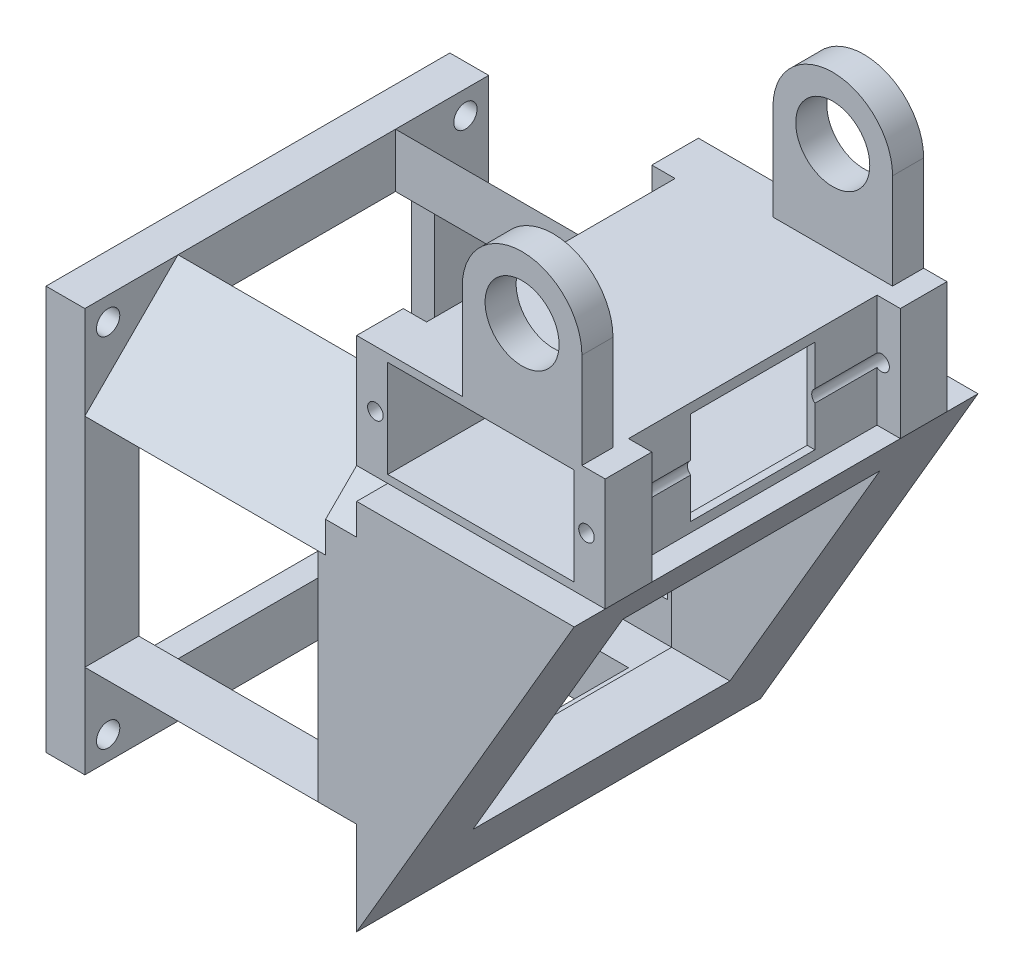
SolidWorks part; units mm, degrees
material "ABS"
ref_plane "Front Plane" through (0, 0, 0) normal (0, 0, 1) x (1, 0, 0)
ref_plane "Top Plane" through (0, 0, 0) normal (0, 1, 0) x (1, 0, 0)
ref_plane "Right Plane" through (0, 0, 0) normal (1, 0, 0) x (0, 0, -1)
sketch "Sketch1" plane through (0, 0, 0) normal (0, 0, 1) x (1, 0, 0)
  line L1 (0, 0) -> (24, 0)
  line L2 (0, 0) -> (0, 12.5)
  line L3 (0, 12.5) -> (24, 12.5)
  line L4 (24, 0) -> (24, 12.5)
  line L5 (-1, -1) -> (25, -1)
  line L6 (-1, -1) -> (-1, 13.5)
  line L7 (-1, 13.5) -> (25, 13.5)
  line L8 (25, -1) -> (25, 13.5)
  dimension "D1" = 24
  dimension "D2" = 12.5
  dimension "D3" = 1
  dimension "D4" = 1
  dimension "D5" = 1
  dimension "D6" = 1
extrude "Boss-Extrude1" add sketch "Sketch1" along normal blind 22
sketch "Sketch2" plane through (0, 0, 22) normal (0, 0, 1) x (1, 0, 0)
  line L0 (12, -1) -> (12, 13.5) construction
  line L1 (-1, 13.5) -> (-4, 13.5)
  line L2 (-1, 13.5) -> (-1, -1)
  line L3 (-1, -1) -> (-4, -1)
  line L4 (-4, 13.5) -> (-4, -1)
  line L5 (-1, -1) -> (25, -1) construction
  line L6 (25, 13.5) -> (-1, 13.5) construction
  line L7 (25, -1) -> (28, -1)
  line L8 (28, 13.5) -> (28, -1)
  line L9 (25, 13.5) -> (28, 13.5)
  line L10 (25, 13.5) -> (25, -1)
  dimension "D1" = 3
  dimension "D2" = 14.5
extrude "Boss-Extrude2" add sketch "Sketch2" against normal blind 6
mirror "Mirror2" about plane through (0, 0, 0) normal (0, 0, -1) of "Boss-Extrude2", "Boss-Extrude1"
sketch "Sketch3" plane through (-1, 0, 0) normal (-1, 0, 0) x (0, 0, 1)
  line L0 (0, -1) -> (0, 13.5) construction
  line L1 (16, -1) -> (-16, -1) construction
  line L2 (16, 13.5) -> (-16, 13.5) construction
  line L4 (-8, 0.25) -> (8, 0.25)
  line L5 (-8, 0.25) -> (-8, 12.25)
  line L6 (-8, 12.25) -> (8, 12.25)
  line L7 (8, 0.25) -> (8, 12.25)
  line L8 (-8, 0.25) -> (8, 12.25) construction
  line L9 (-8, 12.25) -> (8, 0.25) construction
  point P6 (0, 6.25)
  dimension "D1" = 16
  dimension "D2" = 12
extrude "Cut-Extrude1" cut sketch "Sketch3" against normal up to surface (26 mm away) up to face at (25, 6.25, 0)
sketch "Sketch4" plane through (0, 0, 22) normal (0, 0, 1) x (1, 0, 0)
  line L0 (12, 13.5) -> (12, -1) construction
  line L1 (28, 13.5) -> (-4, 13.5) construction
  line L2 (-4, -1) -> (28, -1) construction
  circle A0 centre (-1.59, 6.25) radius 1
  circle A1 centre (25.59, 6.25) radius 1
  dimension "D2" = 2
  dimension "D1" = 13.59
  dimension "D3" = 7.25
extrude "Cut-Extrude2" cut sketch "Sketch4" against normal up to surface (44 mm away)
sketch "Sketch5" plane through (0, 0, 0) normal (1, 0, 0) x (0, 0, -1)
  line L0 (0, 0) -> (0, -48.5226) construction
  line L5 (-16, -1) -> (16, -1) construction
  line L6 (-22, -45) -> (22, -45)
  line L7 (-22, -45) -> (-22, -1)
  line L8 (-22, -1) -> (22, -1)
  line L9 (22, -45) -> (22, -1)
  line L10 (-22, -45) -> (22, -1) construction
  line L11 (-22, -1) -> (22, -45) construction
  line L13 (-19.05, -3.95) -> (19.05, -3.95)
  line L14 (-19.05, -3.95) -> (-19.05, -42.05)
  line L15 (-19.05, -42.05) -> (19.05, -42.05)
  line L16 (19.05, -3.95) -> (19.05, -42.05)
  point P2 (0, -23)
  dimension "D1" = 44
  dimension "D2" = 44
  dimension "D3" = 38.1
  dimension "D4" = 38.1
  dimension "D5" = 2.95
  dimension "D6" = 2.95
extrude "Boss-Extrude3" add sketch "Sketch5" against normal blind 40
sketch "Sketch6" plane through (-40, 0, 0) normal (-1, 0, 0) x (0, 0, 1)
  line L0 (16, -1) -> (-16, -1) construction
  line L2 (22, -1) -> (22, -45) construction
  circle A0 centre (0, -23) radius 25
  dimension "D1" = 50
  dimension "D2" = 22
  dimension "D3" = 22
sketch "Sketch8" plane through (-40, 0, 0) normal (-1, 0, 0) x (0, 0, 1)
  line L0 (-22, -1) -> (22, -1) construction
  line L1 (-26, 3) -> (26, 3)
  line L2 (-26, 3) -> (-26, -49)
  line L3 (-26, -49) -> (26, -49)
  line L4 (26, 3) -> (26, -49)
  line L5 (22, -1) -> (22, -45) construction
  line L6 (0, -1) -> (0, -23)
  line L7 (-22, -1) -> (22, -1)
  line L8 (-22, -1) -> (-22, -45)
  line L9 (-22, -45) -> (22, -45)
  line L10 (22, -1) -> (22, -45)
  line M12 (22, -1) -> (-22, -1)
  line M13 (-22, -1) -> (-22, -45)
  line M22 (-22, -45) -> (22, -45)
  line M23 (22, -45) -> (22, -1)
  dimension "D1" = 52
  dimension "D2" = 52
  dimension "D3" = 4
  dimension "D4" = 4
  dimension "D8" = 22
extrude "Boss-Extrude5" add sketch "Sketch8" against normal up to surface (36 mm away) contours L4 L1 L2 L3 M13 M12 M23 M22 region at (-40, 2.2646, 0) up to face at (-4, 6.25, -19)
extrude "Cut-Extrude5" cut sketch "Sketch6" against normal blind 2
sketch "Sketch9" plane through (-4, 0, 0) normal (1, 0, 0) x (0, 0, -1)
  line L2 (-26, -49) -> (26, -49)
  line L6 (22, -45) -> (-22, -45)
  line L8 (-22, -1) -> (-26, -1)
  line L9 (-26, 3) -> (-26, -49) construction
  line L10 (-26, -1) -> (-26, -49)
  line L11 (22, -1) -> (26, -1)
  line L12 (26, 3) -> (26, -49) construction
  line L13 (26, -1) -> (26, -49)
  line L14 (22, -1) -> (22, -45)
  line L15 (-22, -1) -> (-22, -45)
extrude "Boss-Extrude6" add sketch "Sketch9" along normal up to surface (4 mm away) up to face at (0, -23, 0)
chamfer "Chamfer1" distance 12 angle 45 4 edges at (-22, 3, 26) (-22, 3, -26) (-20, -49, -26) (-20, -49, 26)
sketch "Sketch11" plane through (0, 0, 26) normal (0, 0, 1) x (1, 0, 0)
  line L8 (-40, -9) -> (-40, 3) construction
  line L9 (-35, -9) -> (-5, -9)
  line L10 (-35, -9) -> (-35, -37)
  line L11 (-35, -37) -> (-5, -37)
  line L12 (-5, -9) -> (-5, -37)
  line L14 (0, -37) -> (0, -1) construction
  line L16 (-4, -9) -> (-40, -9) construction
  line L17 (-40, -37) -> (0, -37) construction
  dimension "D2" = 5
  dimension "D3" = 5
extrude "Cut-Extrude7" cut sketch "Sketch11" against normal up to surface (52 mm away) contours L10 L11 L12 L9 up to face at (-14.6667, -15.6667, -26)
sketch "Sketch12" plane through (0, 3, 0) normal (0, 1, 0) x (1, 0, 0)
  line L0 (-4, 14) -> (-40, 14) construction
  line L1 (-35, 14) -> (-5, 14)
  line L2 (-35, 14) -> (-35, -14)
  line L3 (-35, -14) -> (-5, -14)
  line L4 (-5, 14) -> (-5, -14)
  line L5 (-40, -14) -> (-4, -14) construction
  line L6 (0, 22) -> (0, 26) construction
  line L7 (-40, 14) -> (-40, -14) construction
  dimension "D1" = 5
  dimension "D2" = 5
extrude "Cut-Extrude8" cut sketch "Sketch12" against normal up to surface (52 mm away) up to face at (-20, -49, 0)
chamfer "Chamfer3" distance 4 2 edges at (-2, -1, -26) (-2, -1, 26)
sketch "Sketch14" plane through (-40, 0, 0) normal (-1, 0, 0) x (0, 0, 1)
  line L0 (-26, -9) -> (-26, 3)
  line L1 (-26, 3) -> (-14, 3)
  line L2 (-14, 3) -> (-26, -9)
  line L3 (0, -3.95) -> (0, -22.95)
  line L4 (-16.1894, -3.95) -> (16.1894, -3.95) construction
  line L5 (26, -9) -> (14, 3)
  line L6 (14, 3) -> (26, 3)
  line L7 (26, 3) -> (26, -9)
  line L8 (14, -49) -> (26, -37)
  line L9 (26, -37) -> (26, -49)
  line L10 (26, -49) -> (14, -49)
  line L11 (-26, -37) -> (-14, -49)
  line L12 (-14, -49) -> (-26, -49)
  line L13 (-26, -49) -> (-26, -37)
  line L14 (-14, 3) -> (14, 3) construction
  line L15 (26, -9) -> (26, -37) construction
  circle A0 centre (-23, 0) radius 1.5
  circle A1 centre (23, 0) radius 1.5
  circle A2 centre (23, -46) radius 1.5
  circle A3 centre (-23, -46) radius 1.5
  point P30 (0, -23)
  line M19 (-14, 3) -> (-26, -9)
  line M21 (-26, -37) -> (-14, -49)
  line M23 (14, -49) -> (26, -37)
  line M25 (26, -9) -> (14, 3)
  dimension "D1" = 3
  dimension "D2" = 3
  dimension "D3" = 3
  dimension "D4" = 19
  dimension "D5" = 4
extrude "Boss-Extrude7" add sketch "Sketch14" against normal blind 5 contours L1 L0 A0 M19 | L7 L6 L5 A1 M25 | L10 L9 A2 M23 | L13 L12 A3 M21 region at (-40, -1.1089, -21.8911) region at (-40, -1.1089, 21.8911) region at (-40, -44.8911, 21.8911) region at (-40, -44.8911, -21.8911)
sketch "Sketch15" plane through (0, 0, 0) normal (1, 0, 0) x (0, 0, -1)
  line L1 (-19.05, -3.95) -> (19.05, -3.95)
  line L2 (-19.05, -3.95) -> (-19.05, -42.05)
  line L3 (-19.05, -42.05) -> (19.05, -42.05)
  line L4 (19.05, -3.95) -> (19.05, -42.05)
  line L5 (-16.55, -6.45) -> (16.55, -6.45)
  line L6 (-16.55, -6.45) -> (-16.55, -39.55)
  line L7 (-16.55, -39.55) -> (16.55, -39.55)
  line L8 (16.55, -6.45) -> (16.55, -39.55)
  dimension "D1" = 2.5
  dimension "D2" = 2.5
  dimension "D3" = 2.5
  dimension "D4" = 2.5
extrude "Boss-Extrude8" add sketch "Sketch15" against normal blind 2
sketch "Sketch16" plane through (0, 13.5, 0) normal (0, 1, 0) x (1, 0, 0)
  line L0 (0, 0) -> (25, 0) construction
  line L1 (25, -16) -> (25, 16) construction
  line L7 (25, -18) -> (9.6, -18)
  line L8 (28, 22) -> (-4, 22) construction
  line L18 (9.6, -22) -> (9.6, -18)
  line L19 (25, 22) -> (9.6, 22)
  line L20 (25, 22) -> (25, 18)
  line L21 (25, 18) -> (9.6, 18)
  line L22 (9.6, 22) -> (9.6, 18)
  line L23 (25, -22) -> (9.6, -22)
  line L24 (25, -22) -> (25, -18)
  dimension "D1" = 4
  dimension "D2" = 15.4
extrude "Boss-Extrude9" add sketch "Sketch16" along normal blind 20
sketch "Sketch18" plane through (0, 0, 22) normal (0, 0, 1) x (1, 0, 0)
  line L0 (25, 33.5) -> (25, 13.5) construction
  line L2 (9.6, 13.5) -> (-4, 13.5) construction
  circle A0 centre (17.3, 25.5) radius 4.765
  dimension "D1" = 9.53
  dimension "D2" = 7.7
  dimension "D3" = 12
extrude "Cut-Extrude10" cut sketch "Sketch18" against normal up to surface (44 mm away) up to face at (12, 6.25, -22)
fillet "Fillet4" 2 edges at (9.6, 33.5, 20) (25, 33.5, 20) type full round first side face at (9.6, 23.5, 20) second side face at (25, 23.5, 20) middle face at (17.3, 33.5, 20)
fillet "Fillet5" 2 edges at (9.6, 33.5, -20) (25, 33.5, -20) type full round first side face at (9.6, 23.5, -20) second side face at (25, 23.5, -20) middle face at (17.3, 33.5, -20)
sketch "Sketch19" plane through (0, 0, 26) normal (0, 0, 1) x (1, 0, 0)
  line L0 (0, -49) -> (28, -1)
  line L1 (28, -1) -> (0, -1)
  line L2 (0, -1) -> (0, -49)
extrude "Boss-Extrude10" add sketch "Sketch19" against normal up to surface (52 mm away) up to face at (-3, -17, -26)
extrude "Cut-Extrude12" cut sketch "Sketch15<3>" along normal up to surface (24.8208 mm away) contours L8 L7 L6 L5 up to face at (16.8, -20.2, 0)
sketch "Sketch15<3>" plane through (0, 0, 0) normal (1, 0, 0) x (0, 0, -1) same geometry as "Sketch15"
